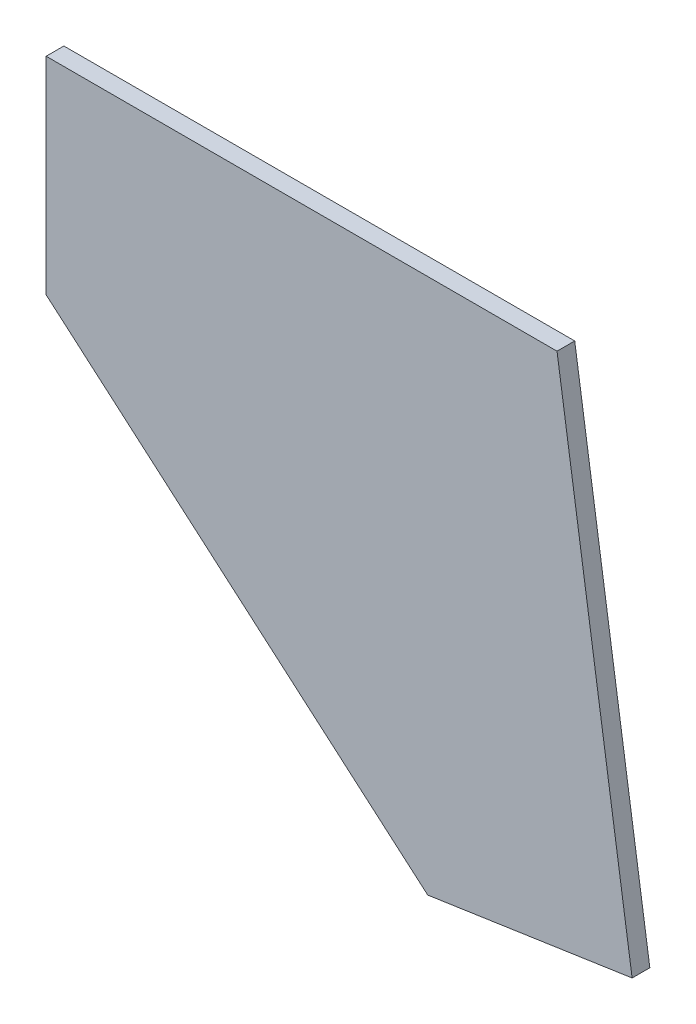
SolidWorks part; units mm, degrees
material "AISI 1020"
ref_plane "Спереди" through (0, 0, 0) normal (0, 0, 1) x (1, 0, 0)
ref_plane "Сверху" through (0, 0, 0) normal (0, 1, 0) x (1, 0, 0)
ref_plane "Справа" through (0, 0, 0) normal (1, 0, 0) x (0, 0, -1)
sketch "Эскиз1" plane through (0, 0, 0) normal (0, 0, 1) x (1, 0, 0)
  line L0 (-43.1169, -50) -> (-216.1672, -50)
  line L1 (-216.1672, -50) -> (-216.1672, -120)
  line L2 (-216.1672, -120) -> (-86.9119, -231.4618)
  line L3 (-86.9119, -231.4618) -> (-17.6727, -221.1694)
  line L4 (-17.6727, -221.1694) -> (-43.1169, -50)
  line L5 (-86.2338, -100) -> (279.4442, -2560) construction
  line L6 (14.865, -100) -> (-4119.457, -100) construction
  line L7 (-86.2338, -100) -> (-151.5395, -175.7309) construction
  point P14 (-151.5395, -175.7309)
  dimension "D1" = 50
  dimension "D2" = 20
  dimension "D3" = 50
  dimension "D4" = 20
  dimension "D5" = 100
base flange "Базовая кромка1" sketch "Эскиз1" thickness 6 reverse thickness direction no parameters "D1"=0.75
sketch "Сгиб-Линии1" plane through (0, 0, 0) normal (0, 1, 0) x (1, 0, 0)
sketch "Граничная рамка1" plane through (0, 0, 0) normal (0, 1, 0) x (1, 0, 0)
sheet metal parameters "Листовой металл3" thickness 6 parameters "D1"=0.75
flat pattern "Развертка3" [suppressed]
sketch "Сгиб-Линии2" plane through (0, 0, 0) normal (0, 1, 0) x (1, 0, 0)
sketch "Граничная рамка2" [suppressed] plane through (0, 0, 0) normal (0, 1, 0) x (1, 0, 0)
